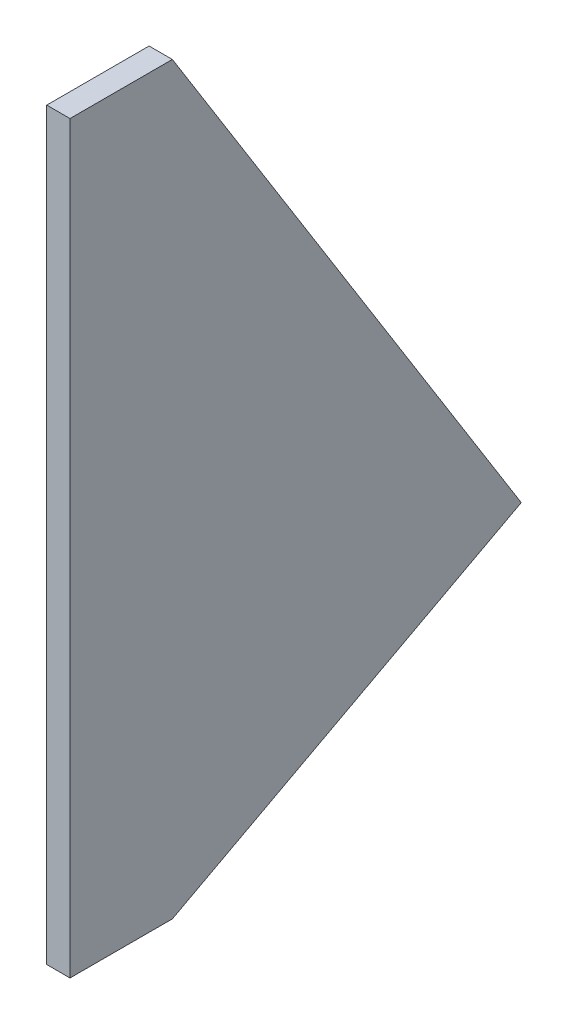
SolidWorks part; units mm, degrees
material "Thornel Mat VMA"
ref_plane "Front Plane" through (0, 0, 0) normal (0, 0, 1) x (1, 0, 0)
ref_plane "Top Plane" through (0, 0, 0) normal (0, 1, 0) x (1, 0, 0)
ref_plane "Right Plane" through (0, 0, 0) normal (1, 0, 0) x (0, 0, -1)
sketch "Sketch1" plane through (0, 0, 0) normal (1, 0, 0) x (0, 0, -1)
  line L0 (0, 0) -> (0, 203.2)
  line L1 (0, 203.2) -> (27.94, 203.2)
  line L2 (27.94, 203.2) -> (123.19, 50.8)
  line L3 (123.19, 50.8) -> (27.94, 0)
  line L4 (27.94, 0) -> (0, 0)
  dimension "D1" = 203.2
  dimension "D2" = 152.4
  dimension "D3" = 95.25
  dimension "D4" = 27.94
extrude "Boss-Extrude1" add sketch "Sketch1" along normal mid plane 6.35
